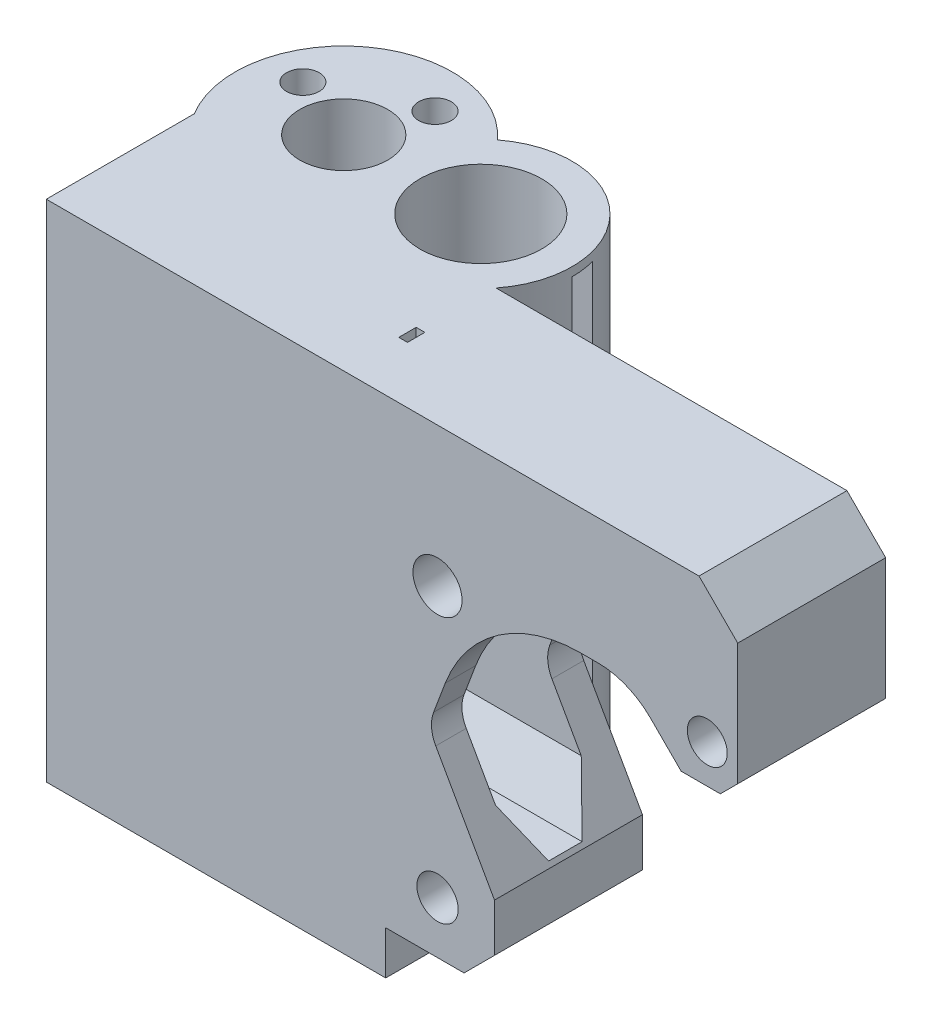
SolidWorks part; units mm, degrees
ref_plane "Front Plane" through (0, 0, 0) normal (0, 0, 1) x (1, 0, 0)
ref_plane "Top Plane" through (0, 0, 0) normal (0, 1, 0) x (1, 0, 0)
ref_plane "Right Plane" through (0, 0, 0) normal (1, 0, 0) x (0, 0, -1)
sketch "Sketch1" plane through (0, 0, 0) normal (0, 0, 1) x (1, 0, 0)
  line L0 (39, -53) -> (48, -53)
  line L1 (0, 0) -> (39, 0)
  line L2 (0, 0) -> (0, -58)
  line L3 (0, -58) -> (39, -58)
  line L4 (39, -53) -> (39, -58)
  line L5 (39, 0) -> (75, 0)
  line L6 (75, 0) -> (79.45, -4.45)
  line L7 (79.45, -4.45) -> (79.45, -18.45)
  line L8 (79.45, -18.45) -> (77.45, -20.45)
  line L9 (77.45, -20.45) -> (72.95, -20.45)
  line L10 (72.95, -20.45) -> (69.45, -16.95)
  line L12 (45.8405, -25.2376) -> (44.5009, -28.8048)
  line L13 (44.75, -32.0294) -> (51.5, -44)
  line L14 (51.5, -44) -> (51.5, -49.5)
  line L15 (61.4145, -14.45) -> (63.4145, -14.45)
  line L16 (51.5, -49.5) -> (48, -53)
  arc A5 (63.4145, -14.45) -> (69.45, -16.95) centre (63.4145, -22.9855) cw
  arc A6 (61.4145, -14.45) -> (45.8405, -25.2376) centre (61.4145, -31.0859) ccw
  arc A7 (44.5009, -28.8048) -> (44.75, -32.0294) centre (48.083, -30.15) ccw
  dimension "D1" = 58
  dimension "D2" = 39
  dimension "D3" = 75
  dimension "D4" = 4.45
  dimension "D5" = 135
  dimension "D6" = 14
  dimension "D7" = 2
  dimension "D8" = 3.5
  dimension "D9" = 6
  dimension "D10" = 5
  dimension "D11" = 4.5
  dimension "D12" = 130
  dimension "D13" = 3.5
  dimension "D14" = 5.5
  dimension "D15" = 6.75
  dimension "D16" = 9
  dimension "D17" = 13.85
  dimension "D18" = 3.417
  dimension "D19" = 2
extrude "Boss-Extrude1" add sketch "Sketch1" along normal blind 17
sketch "Sketch2" plane through (0, 0, 0) normal (0, 1, 0) x (1, 0, 0)
  line L0 (0, -17) -> (0, 6.5) construction
  line L1 (0, 6.5) -> (26.427, 6.5) construction
  circle A0 centre (26.427, 6.5) radius 10.5
  dimension "D2" = 21
  dimension "D1" = 23.5
  dimension "D3" = 26.427
extrude "Boss-Extrude2" add sketch "Sketch2" against normal up to surface (58 mm away) up to face at (19.5, -58, 8.5)
sketch "Sketch3" plane through (0, 0, 0) normal (0, 1, 0) x (1, 0, 0)
  line L0 (0, -17) -> (0, 20.4292) construction
  line L1 (10.6771, 6.5) -> (0, 6.5) construction
  line L2 (75, -17) -> (0, -17) construction
  circle A0 centre (10.6771, 6.5) radius 12.5
  dimension "D3" = 25
  dimension "D2" = 23.5
extrude "Boss-Extrude3" add sketch "Sketch3" against normal blind 13.5
sketch "Sketch4" plane through (0, 0, 0) normal (0, 1, 0) x (1, 0, 0)
  circle A0 centre (26.427, 6.5) radius 7
  circle A1 centre (10.6771, 6.5) radius 5.05
  dimension "D1" = 10.1
  dimension "D2" = 14
extrude "Cut-Extrude1" cut sketch "Sketch4" against normal through all
sketch "Sketch5" plane through (0, 0, 0) normal (-1, 0, 0) x (0, 0, 1)
  line L0 (10.5, -43.5) -> (6.65, -43.5)
  line L1 (6.65, -43.5) -> (3.65, -38)
  line L2 (3.65, -38) -> (3.65, -19)
  line L3 (3.65, -19) -> (6.65, -16)
  line L4 (6.65, -16) -> (10.5, -16)
  line L5 (10.5, -16) -> (13.5, -19)
  line L6 (13.5, -19) -> (13.5, -38)
  line L7 (13.5, -38) -> (10.5, -43.5)
  line L8 (17, 0) -> (0, 0) construction
  line L9 (17, 0) -> (17, -58) construction
  circle A0 centre (8.5, -6) radius 4.05
  circle A1 centre (8.5, -51) radius 4.05
  dimension "D8" = 8.1
  dimension "D9" = 8.1
  dimension "D1" = 19
  dimension "D2" = 3
  dimension "D3" = 3.85
  dimension "D4" = 16
  dimension "D5" = 6
  dimension "D6" = 51
  dimension "D7" = 5.5
  dimension "D10" = 3
  dimension "D11" = 3
  dimension "D12" = 19
  dimension "D13" = 3.85
  dimension "D14" = 3
  dimension "D15" = 3
  dimension "D16" = 3.5
  dimension "D17" = 8.5
  dimension "D18" = 8.5
extrude "Cut-Extrude2" cut sketch "Sketch5" against normal blind 35
sketch "Sketch6" plane through (0, 0, 0) normal (0, 0, -1) x (-1, 0, 0)
  line L0 (-75.9503, -16.0252) -> (-44.9503, -16.0252) construction
  line L1 (-44.9503, -16.0252) -> (-44.9503, -47.0252) construction
  line L2 (-44.9503, -47.0252) -> (-75.9503, -47.0252) construction
  line L3 (-75.9503, -47.0252) -> (-75.9503, -16.0252) construction
  line L4 (-75.9503, -31.5252) -> (-44.9503, -31.5252) construction
  line L5 (-60.4503, -16.0252) -> (-60.4503, -47.0252) construction
  circle A0 centre (-75.9503, -16.0252) radius 2.2933
  circle A1 centre (-44.9503, -16.0252) radius 2.8225
  circle A2 centre (-44.9503, -47.0252) radius 2.3733
  circle A3 centre (-60.4503, -31.5252) radius 11 construction
  point P14 (-60.4503, -31.5252)
  dimension "D3" = 22
  dimension "D1" = 31
  dimension "D2" = 31
extrude "Cut-Extrude3" cut sketch "Sketch6" against normal through all
sketch "Sketch8" plane through (35, 0, 0) normal (-1, 0, 0) x (0, 0, 1)
  line L8 (10.5, -43.5) -> (13.5, -38)
  line L9 (13.5, -38) -> (13.5, -19)
  line L10 (13.5, -19) -> (10.5, -16)
  line L11 (10.5, -16) -> (6.65, -16)
  line L12 (6.65, -16) -> (3.65, -19)
  line L13 (3.65, -19) -> (3.65, -38)
  line L14 (3.65, -38) -> (6.65, -43.5)
  line L15 (6.65, -43.5) -> (10.5, -43.5)
  line L16 (10.5, -43.5) -> (13.5, -38)
  line L17 (13.5, -38) -> (13.5, -19)
  line L18 (13.5, -19) -> (10.5, -16)
  line L19 (10.5, -16) -> (6.65, -16)
  line L20 (6.65, -16) -> (3.65, -19)
  line L21 (3.65, -19) -> (3.65, -38)
  line L22 (3.65, -38) -> (6.65, -43.5)
  line L23 (6.65, -43.5) -> (10.5, -43.5)
  dimension "D1" = 0
extrude "Cut-Extrude4" cut sketch "Sketch8" against normal blind 20
sketch "Sketch10" plane through (0, 0, 0) normal (0, 1, 0) x (1, 0, 0)
  line L0 (13.5702, 14.0925) -> (10.6771, 6.5) construction
  line L1 (10.6771, 6.5) -> (3.0846, 9.3931) construction
  circle A0 centre (13.5702, 14.0925) radius 1.875
  circle A1 centre (3.0846, 9.3931) radius 1.875
  dimension "D3" = 3.75
  dimension "D4" = 3.75
  dimension "D1" = 90
  dimension "D2" = 8.125
  dimension "D5" = 8.125
extrude "Cut-Extrude6" cut sketch "Sketch10" against normal through all
sketch "Sketch11" plane through (0, -58, 0) normal (0, -1, 0) x (1, 0, 0)
  line L0 (0, 17) -> (0, 0) construction
  line L1 (35, 8.5) -> (34, 8.5)
  line L2 (35, 8.5) -> (35, 10.5)
  line L3 (35, 10.5) -> (34, 10.5)
  line L4 (34, 8.5) -> (34, 10.5)
  line L5 (0, 17) -> (39, 17) construction
  dimension "D1" = 35
  dimension "D2" = 1
  dimension "D3" = 2
  dimension "D4" = 6.5
extrude "Cut-Extrude7" cut sketch "Sketch11" against normal blind 8
ref_plane "Plane1" through (0, -29, 0) normal (0, 1, 0) x (1, 0, 0)
mirror "Mirror1" about plane through (0, -29, 0) normal (0, 1, 0) of "Cut-Extrude7"
sketch "Sketch13" plane through (0, -58, 0) normal (0, -1, 0) x (1, 0, 0)
  line L0 (26.427, -6.5) -> (36.5692, -9.2176) construction
  line L1 (26.427, -6.5) -> (9.2701, -6.5) construction
  line L2 (26.427, -6.5) -> (36.927, -6.5) construction
  line L3 (33.1885, -8.3117) -> (36.5692, -9.2176)
  line L4 (36.927, -6.5) -> (33.427, -6.5)
  arc A0 (33.1885, -8.3117) -> (33.427, -6.5) centre (26.427, -6.5) ccw
  arc A1 (15.927, -6.5) -> (36.927, -6.5) centre (26.427, -6.5) ccw construction
  arc A2 (18.1808, 0) -> (34.6732, 0) centre (26.427, -6.5) ccw construction
  circle A3 centre (26.427, -6.5) radius 7 construction
  dimension "D1" = 15
  dimension "D2" = 180
extrude "Cut-Extrude9" cut sketch "Sketch13" against normal blind 57 and the other way through all
